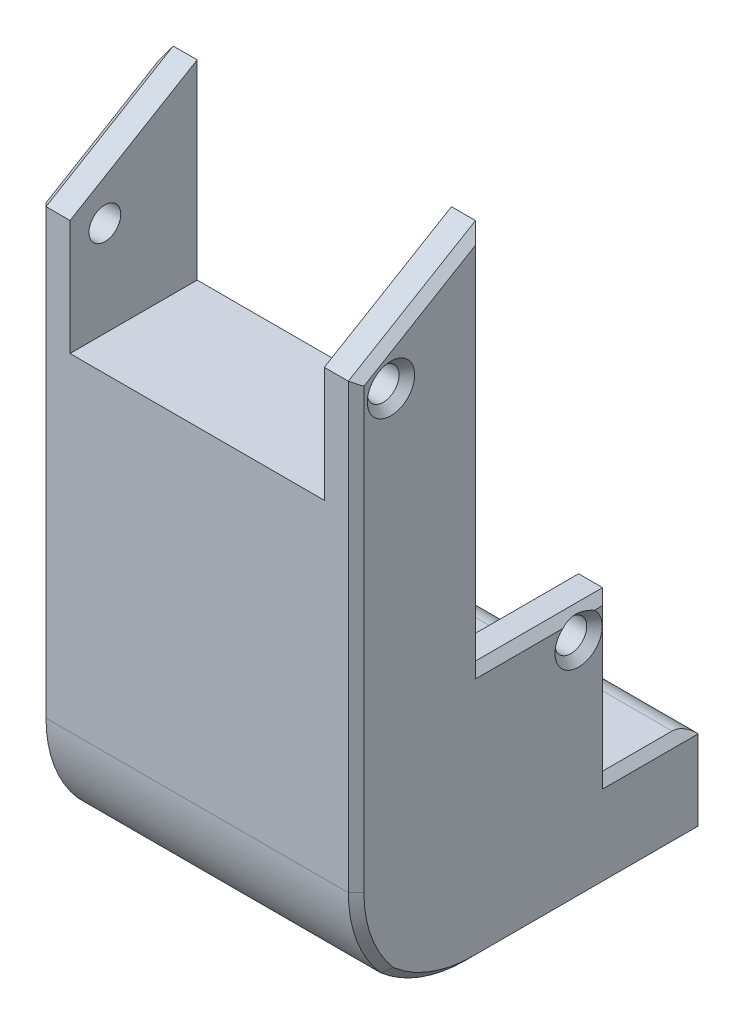
SolidWorks part; units mm, degrees
ref_plane "前视基准面" through (0, 0, 0) normal (0, 0, 1) x (1, 0, 0)
ref_plane "上视基准面" through (0, 0, 0) normal (0, 1, 0) x (1, 0, 0)
ref_plane "右视基准面" through (0, 0, 0) normal (1, 0, 0) x (0, 0, -1)
other "Configuration Table"
sketch "草图1" plane through (0, 0, 0) normal (0, 0, 1) x (1, 0, 0)
  line L1 (2.5, 5) -> (-2.5, 5)
  line L2 (2.5, 5) -> (2.5, -5)
  line L3 (2.5, -5) -> (-2.5, -5)
  line L4 (-2.5, 5) -> (-2.5, -5)
  line L5 (2.5, 5) -> (-2.5, -5) construction
  line L6 (2.5, -5) -> (-2.5, 5) construction
  point P0 (0, 0)
  dimension "D1" = 5
  dimension "D2" = 10
extrude "凸台-拉伸1" add sketch "草图1" along normal blind 4
sketch "草图2" plane through (2.5, 0, 0) normal (1, 0, 0) x (0, 0, -1)
  line L1 (-4, 3.8119) -> (-2, 5)
  line L3 (-4, -5) -> (-4, 5) construction
  line L6 (-4, 5) -> (0, 5) construction
extrude "切除-拉伸1" cut sketch "草图2" against normal through all and the other way through all
sketch "草图3" plane through (2.5, 0, 0) normal (1, 0, 0) x (0, 0, -1)
  line L0 (-2, 5) -> (-2, -1)
  line L1 (-2, -1) -> (0, -1)
  line L2 (0, -5) -> (0, 5) construction
  point P3 (-3, 5)
  point P7 (0, 0)
  point P8 (0, 0)
  point P10 (0, 0)
  point P11 (0, 0)
  dimension "D1" = 6
extrude "切除-拉伸2" cut sketch "草图3" against normal through all and the other way through all contours L0 L1
sketch "草图6" plane through (0, -1, 0) normal (0, 1, 0) x (1, 0, 0)
  line L0 (2.5, 0) -> (-2.5, 0) construction
  line L1 (-2, -3) -> (2, -3)
  line L2 (-2, -3) -> (-2, 0)
  line L3 (-2, 0) -> (2, 0)
  line L4 (2, -3) -> (2, 0)
  line L5 (-2, -3) -> (2, 0) construction
  line L6 (-2, 0) -> (2, -3) construction
  line L7 (-2.5, 0) -> (-2.5, -2) construction
  point P0 (0, -1.5)
  dimension "D1" = 4
  dimension "D2" = 3
  dimension "D3" = 0.5
extrude "切除-拉伸3" cut sketch "草图6" against normal blind 2.5
sketch "草图7" plane through (0, 0, 2) normal (0, 0, -1) x (-1, 0, 0)
  line L0 (-2.5, 5) -> (2.5, 5) construction
  line L1 (2, 5) -> (-2, 5)
  line L2 (2, 5) -> (2, 2)
  line L3 (2, 2) -> (-2, 2)
  line L4 (-2, 5) -> (-2, 2)
  line L5 (2, 5) -> (-2, 2) construction
  line L6 (2, 2) -> (-2, 5) construction
  line L7 (-2.5, 5) -> (-2.5, -1) construction
  point P0 (0, 3.5)
  dimension "D1" = 4
  dimension "D2" = 3
  dimension "D3" = 0.5
extrude "切除-拉伸4" cut sketch "草图7" against normal blind 2.5
sketch "草图8" plane through (2.5, 0, 0) normal (1, 0, 0) x (0, 0, -1)
  line L0 (-4, -5) -> (-4, 3.8119) construction
  line L1 (-4, -5) -> (0, -5) construction
  line L2 (-4, -4) -> (-3, -5)
  point P0 (-4, -4)
  point P1 (-3, -5)
  dimension "D1" = 1
  dimension "D2" = 1
extrude "切除-拉伸5" cut sketch "草图8" against normal through all and the other way through all flip side to cut
sketch "草图9" plane through (2.5, 0, 0) normal (1, 0, 0) x (0, 0, -1)
  line L0 (0, -5) -> (0, -1) construction
  line L1 (-3, -5) -> (0, -5) construction
  line L2 (-1.5, -5) -> (0, -3.5)
  point P0 (0, -3.5)
  point P1 (-1.5, -5)
  dimension "D1" = 2.5
extrude "切除-拉伸10" cut sketch "草图9" against normal blind 5 and the other way through all flip side to cut contours L2
sketch "草图11" plane through (2.5, 0, 0) normal (1, 0, 0) x (0, 0, -1)
  line L0 (-4, -4) -> (-4, 3.8119) construction
  line L1 (-3, -5) -> (-1.5, -5) construction
  circle A1 centre (-3.4519, 3.5) radius 0.25
  dimension "D1" = 0.5
  dimension "D2" = 0.5481
  dimension "D3" = 8.5
extrude "切除-拉伸11" cut sketch "草图11" against normal blind 5
sketch "草图12" plane through (2.5, 0, 0) normal (1, 0, 0) x (0, 0, -1)
  line L0 (-2, -1) -> (0, -1) construction
  line L1 (0, -3.5) -> (0, -1) construction
  circle A1 centre (-0.5, -1.4) radius 0.25
  dimension "D1" = 0.5
  dimension "D2" = 0.4
  dimension "D3" = 0.5
extrude "切除-拉伸12" cut sketch "草图12" against normal blind 5
sketch "草图14" plane through (-2.5, 0, 0) normal (-1, 0, 0) x (0, 0, 1)
  line L4 (1.5, -5) -> (-1.5, -5)
  line L5 (-1.5, -5) -> (-1.5, -3.5)
  line L6 (-1.5, -3.5) -> (0, -3.5)
  line L7 (0, -3.5) -> (1.5, -5)
  dimension "D1" = 3
extrude "凸台-拉伸3" add sketch "草图14" against normal blind 5
scale "缩放比例1" bodies to scale 118 scale about centroid uniform scaling yes scale factor 2.454545
fillet "圆角1" radius 5 2 edges at (0, -9.4856, 4.231) (0, -7.031, 6.6855)
chamfer "倒角1" distance 0.3 angle 45 24 edges at (6.1364, 3.5918, 6.6855) (6.1364, 7.6962, 1.7764) (6.1364, 0.3326, -0.6781) (6.1364, -2.7356, -3.1327) (6.1364, -5.8038, -4.9736) (6.1364, -7.6447, -6.8145) (6.1364, -9.4856, -2.3273) (6.1364, -9.1666, 3.9172) (6.1364, -6.7173, 6.3665) (6.1364, 11.9917, 5.3402) (6.1364, -0.0356, -1.9054) (-6.1364, -7.6447, -6.8145) (-6.1364, -5.8038, -4.9736) (-6.1364, -2.7356, -3.1327) (-6.1364, 0.3326, -0.6781) (-6.1364, 7.6962, 1.7764) (-6.1364, 3.5918, 6.6855) (-6.1364, -6.7173, 6.3665) (-6.1364, -9.1666, 3.9172) (-6.1364, -9.4856, -2.3273) (-6.1364, 11.9917, 5.3402) (-6.1364, -0.0356, -1.9054) (6.1364, 13.6018, 4.231) (-6.1364, 13.6018, 4.231)
fillet "圆角2" radius 1 2 edges at (0, -5.8038, -6.8145) (0, -9.4856, -6.8145)
